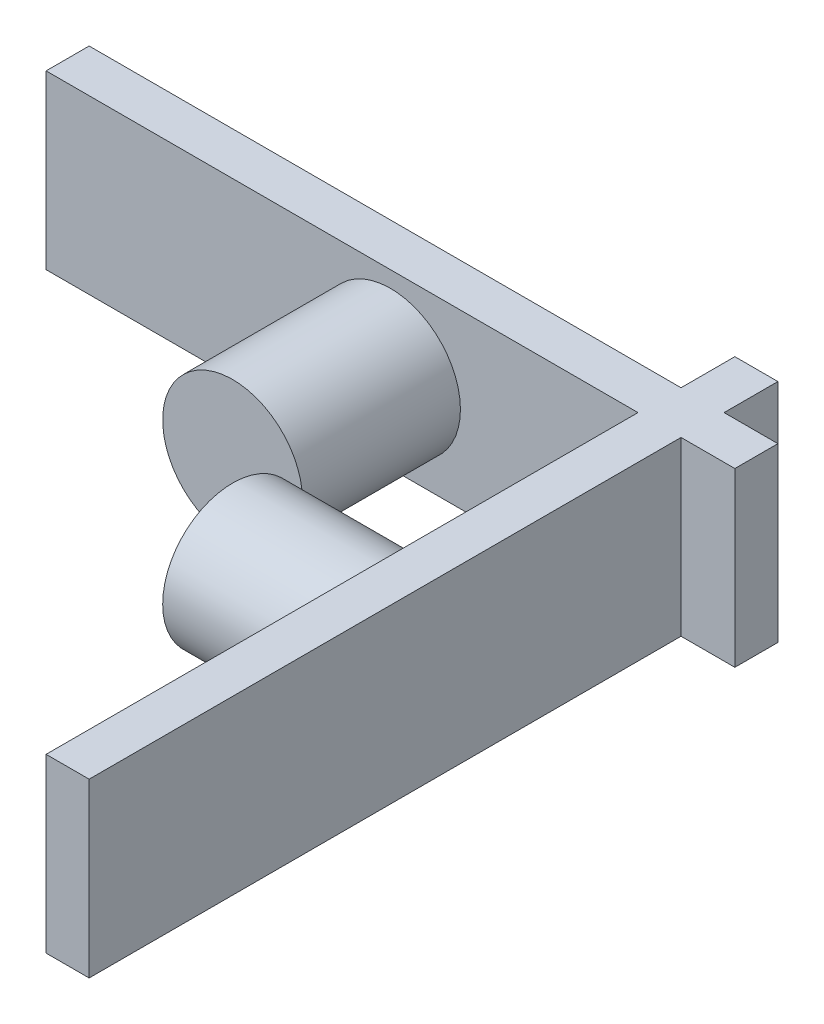
SolidWorks part; units mm, degrees
ref_plane "Front Plane" through (0, 0, 0) normal (0, 0, 1) x (1, 0, 0)
ref_plane "Top Plane" through (0, 0, 0) normal (0, 1, 0) x (1, 0, 0)
ref_plane "Right Plane" through (0, 0, 0) normal (1, 0, 0) x (0, 0, -1)
sketch "Sketch1" plane through (0, 0, 0) normal (0, 0, 1) x (1, 0, 0)
  line L0 (0, 0) -> (0, 6)
  line L9 (-8, 6) -> (8, 6)
  line L10 (-8, 6) -> (-8, -6)
  line L11 (-8, -6) -> (8, -6)
  line L12 (8, 6) -> (8, -6)
  line L13 (0, 0) -> (-8, 0)
  line L14 (0, 0) -> (0, -6)
  line L16 (8, 6) -> (24, 6)
  line L17 (8, 6) -> (8, -6)
  line L18 (8, -6) -> (24, -6)
  line L19 (24, 6) -> (24, -6)
  line L20 (-8, 6) -> (-24, 6)
  line L21 (-8, 6) -> (-8, -6)
  line L22 (-8, -6) -> (-24, -6)
  line L23 (-24, 6) -> (-24, -6)
  circle A0 centre (0, 0) radius 4.875
  dimension "D1" = 9.75
  dimension "D2" = 8
  dimension "D3" = 12
extrude "Boss-Extrude1" add sketch "Sketch1" against normal blind 3 contours A0 L0 L9 L10 L13 | A0 L13 L10 L11 L14 | L13 A0 L14 | L0 A0 L13 | L14 A0 L0 | A0 L14 L11 L12 L9 L0 | L20 L23 L22 L10 | L19 L16 L12 L18 region at (-2.069, 2.069, 0) region at (-2.069, -2.069, 0) region at (2.069, 0, 0) region at (-5.2287, 3.5924, 0) region at (5.2287, 0, 0) region at (-5.2287, -3.5924, 0) region at (-16, 0, 0) region at (16, 0, 0)
extrude "Boss-Extrude2" add sketch "Sketch1<3>" along normal blind 11 contours L0 A0 L13 | L14 A0 L0 | L13 A0 L14 region at (-2.069, 2.069, 0) region at (-2.069, -2.069, 0) region at (2.069, 0, 0)
sketch "Sketch1<3>" plane through (0, 0, 0) normal (0, 0, 1) x (1, 0, 0) same geometry as "Sketch1"
ref_plane "Plane2" through (0, 0, 17.25) normal (0, 0, 1) x (1, 0, 0)
ref_axis "Axis1" through (0, 55, 17.25) along (0, -1, 0)
pattern_circular "CirPattern2" count 2 every 90 about axis through (0, 55, 17.25) along (0, -1, 0) of "Boss-Extrude1", "Boss-Extrude2"
